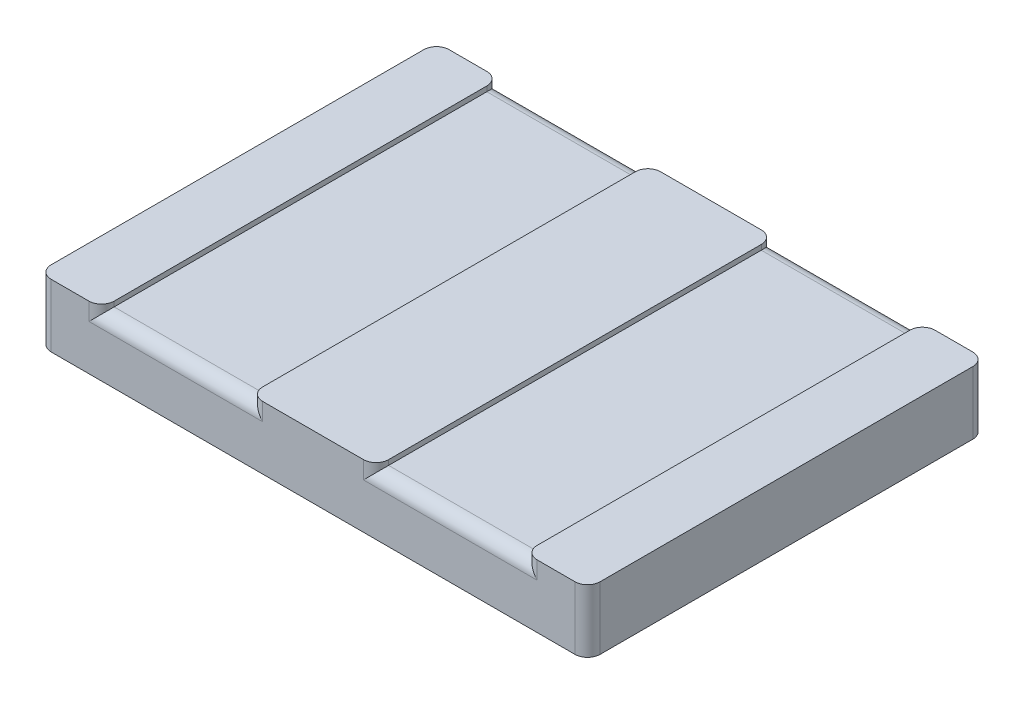
SolidWorks part; units mm, degrees
ref_plane "Спереди" through (0, 0, 0) normal (0, 0, 1) x (1, 0, 0)
ref_plane "Сверху" through (0, 0, 0) normal (0, 1, 0) x (1, 0, 0)
ref_plane "Справа" through (0, 0, 0) normal (1, 0, 0) x (0, 0, -1)
sketch "Эскиз1" plane through (0, 0, 0) normal (0, 0, 1) x (1, 0, 0)
  line L0 (0, 12.209) -> (0, -16.0977) construction
  line L1 (-10.9, 0) -> (10.9, 0)
  line L2 (10.9, 0) -> (10.9, 2.5)
  line L3 (10.9, 2.5) -> (8.4, 2.5)
  line L4 (8.4, 2.5) -> (8.4, 2.3)
  line L5 (8.4, 2.3) -> (2.5, 2.3)
  line L6 (2.5, 2.3) -> (2.5, 2.5)
  line L7 (2.5, 2.5) -> (-2.5, 2.5)
  line L8 (-2.5, 2.3) -> (-2.5, 2.5)
  line L9 (-8.4, 2.3) -> (-2.5, 2.3)
  line L10 (-8.4, 2.5) -> (-8.4, 2.3)
  line L11 (-10.9, 2.5) -> (-8.4, 2.5)
  line L12 (-10.9, 0) -> (-10.9, 2.5)
  point P3 (8.4, 2.4)
  point P12 (0, 2.5)
  point P17 (0, 0)
  dimension "D1" = 10.9
  dimension "D2" = 2.5
  dimension "D3" = 0.2
  dimension "D4" = 2.5
  dimension "D5" = 8.4
extrude "Бобышка-Вытянуть1" add sketch "Эскиз1" along normal blind 7.9 and the other way blind 7.9
fillet "Скругление1" radius 0.5 16 edges at (-5.45, 2.3, -7.9) (-2.5, 2.4, -7.9) (-8.4, 2.4, -7.9) (-10.9, 1.25, -7.9) (2.5, 2.4, -7.9) (5.45, 2.3, -7.9) (8.4, 2.4, -7.9) (10.9, 1.25, -7.9) (10.9, 1.25, 7.9) (8.4, 2.4, 7.9) (5.45, 2.3, 7.9) (2.5, 2.4, 7.9) (-2.5, 2.4, 7.9) (-5.45, 2.3, 7.9) (-8.4, 2.4, 7.9) (-10.9, 1.25, 7.9)
